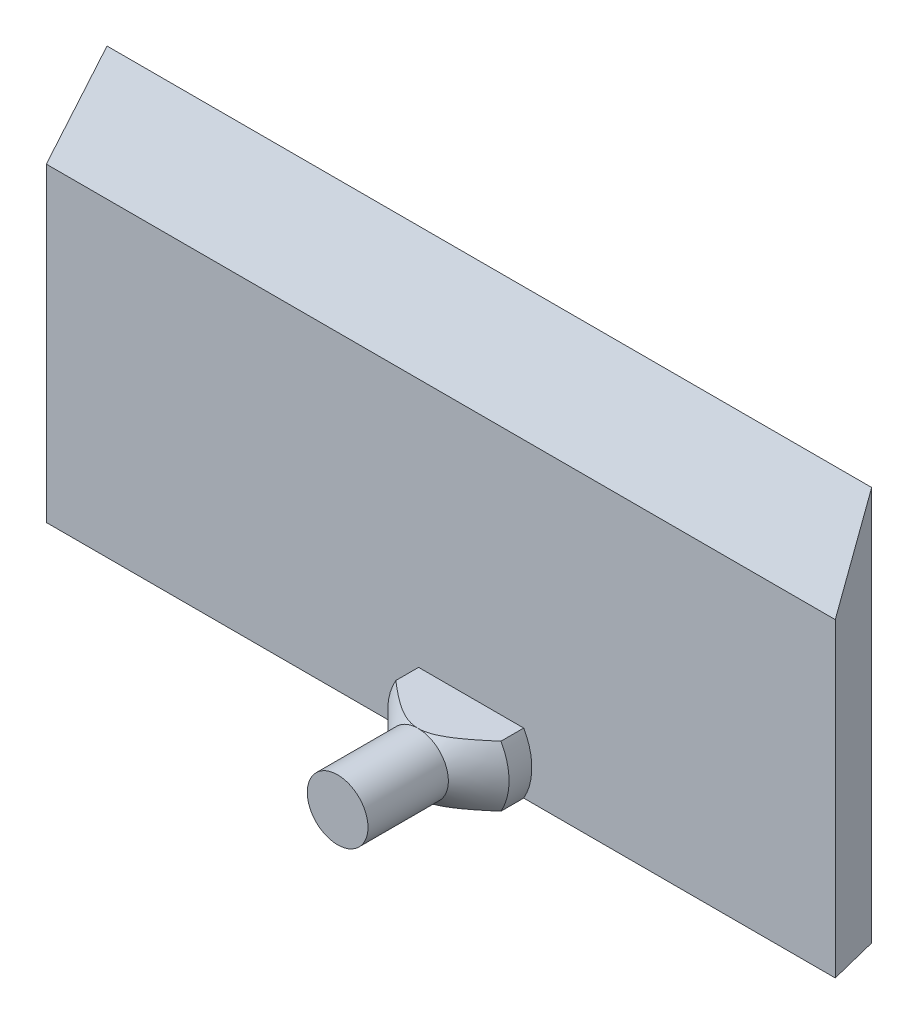
SolidWorks part; units mm, degrees
ref_plane "Ebene vorne" through (0, 0, 0) normal (0, 0, 1) x (1, 0, 0)
ref_plane "Ebene oben" through (0, 0, 0) normal (0, 1, 0) x (1, 0, 0)
ref_plane "Ebene rechts" through (0, 0, 0) normal (1, 0, 0) x (0, 0, -1)
sketch "Skizze1" plane through (0, 0, 0) normal (0, 0, 1) x (1, 0, 0)
  line L0 (1, 6.5) -> (1, -6.3686) construction
  line L1 (-13, 6.5) -> (13, 6.5)
  line L2 (-13, 6.5) -> (-13, -6.5)
  line L3 (-13, -6.5) -> (13, -6.5)
  line L4 (13, 6.5) -> (13, -6.5)
  line L5 (-13, 6.5) -> (13, -6.5) construction
  line L6 (-13, -6.5) -> (13, 6.5) construction
  line L7 (-0.7321, -4.5) -> (2.7321, -4.5)
  circle A0 centre (1, -5.5) radius 1
  circle A1 centre (1, -5.5) radius 2
  point P0 (0, 0)
  point P14 (1, -4.5)
  dimension "D3" = 2
  dimension "D5" = 4
  dimension "D1" = 26
  dimension "D2" = 12
  dimension "13" = 13
  dimension "D4" = 1
extrude "Aufsatz-Linear austragen1" add sketch "Skizze1" along normal blind 1.6 contours A1 L3 L4 L1 L2 | L7 A1 L3 A0 | L3 A1 L7 A0 | A0 | L7 A1 region at (-0.0308, 0.159, 0) region at (-0.33, -5.5, 0) region at (2.33, -5.5, 0) region at (1, -5.5, 0) region at (1, -4.09, 0)
extrude "Aufsatz-Linear austragen2" add sketch "Skizze1<3>" along normal blind 6 contours A0 region at (1, -5.5, 0)
sketch "Skizze1<3>" plane through (0, 0, 0) normal (0, 0, 1) x (1, 0, 0) same geometry as "Skizze1"
extrude "Aufsatz-Linear austragen3" add sketch "Skizze1<4>" along normal blind 3.35 contours L7 A1 L3 A0 | L3 A1 L7 A0 region at (-0.33, -5.5, 0) region at (2.33, -5.5, 0)
sketch "Skizze1<4>" plane through (0, 0, 0) normal (0, 0, 1) x (1, 0, 0) same geometry as "Skizze1"
chamfer "Fase1" distance 1 angle 45 2 edges at (3, -5.5, 3.35) (-1, -5.5, 3.35) tangent propagation no
chamfer "Fase2" distance 1.6 distance2 0.4 1 edges at (13, 0, 0) first distance on face at (13, 0, 0.8)
chamfer "Fase3" distance 0.4 distance2 1.6 1 edges at (-13, 0, 0) first distance on face at (-0.2, 0, 0)
chamfer "Fase4" distance 1.6 angle 60 1 edges at (0, 6.5, 1.6) first distance on face at (0, 6.5, 0.8)
